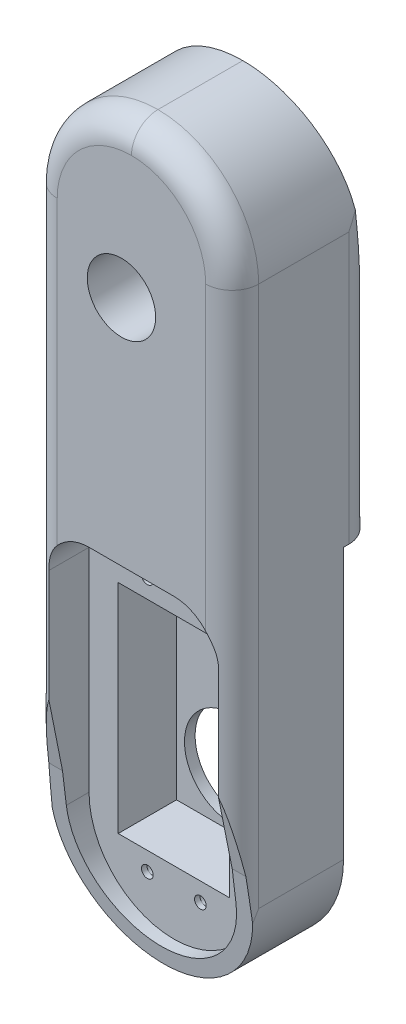
SolidWorks part; units mm, degrees
ref_plane "Front Plane" through (0, 0, 0) normal (0, 0, 1) x (1, 0, 0)
ref_plane "Top Plane" through (0, 0, 0) normal (0, 1, 0) x (1, 0, 0)
ref_plane "Right Plane" through (0, 0, 0) normal (1, 0, 0) x (0, 0, -1)
sketch "Sketch1" plane through (0, 0, 0) normal (0, 0, 1) x (1, 0, 0)
  line L5 (-19, -60) -> (19, -60)
  line L6 (-19, -60) -> (-19, 60)
  line L7 (-19, 60) -> (19, 60)
  line L8 (19, -60) -> (19, 60)
  line L9 (-19, -60) -> (19, 60) construction
  line L10 (-19, 60) -> (19, -60) construction
  line L11 (-10.5, -45) -> (10.5, -45)
  line L12 (-10.5, -45) -> (-10.5, -4)
  line L13 (-10.5, -4) -> (10.5, -4)
  line L14 (10.5, -45) -> (10.5, -4)
  line L15 (-10.5, -45) -> (10.5, -4) construction
  line L16 (-10.5, -4) -> (10.5, -45) construction
  point P0 (0, 0)
  point P6 (0, -24.5)
  dimension "D1" = 21
  dimension "D2" = 41
  dimension "D3" = 8.5
  dimension "D4" = 120
  dimension "D5" = 15
extrude "Boss-Extrude1" add sketch "Sketch1" along normal blind 11
ref_plane "Plane1" through (0, 0, 10) normal (0, 0, 1) x (1, 0, 0)
sketch "Sketch3" plane through (0, 0, 10) normal (0, 0, 1) x (1, 0, 0)
  line L0 (10.5, -4) -> (-10.5, -4) construction
  circle A0 centre (-5, -0.5) radius 1.3
  circle A1 centre (5, -0.5) radius 1.3
  circle A2 centre (5, -48.5) radius 1.3
  circle A3 centre (-5, -48.5) radius 1.3
  dimension "D1" = 2.6
  dimension "D2" = 5
  dimension "D3" = 3.5
  dimension "D4" = 2
  dimension "D5" = 2
extrude "Cut-Extrude1" cut sketch "Sketch3" against normal blind 8
fillet "Fillet3" radius 19 2 edges at (19, -60, 5.5) (-19, -60, 5.5)
sketch "Sketch4" plane through (0, 0, 11) normal (0, 0, 1) x (1, 0, 0)
  line L0 (16, -41) -> (16, 57)
  line L1 (16, 57) -> (-16, 57)
  line L2 (-16, 57) -> (-16, -41)
  line L3 (19, -41) -> (19, 60)
  line L4 (19, 60) -> (-19, 60)
  line L5 (-19, 60) -> (-19, -41)
  line L6 (19, -41) -> (19, 60)
  line L7 (19, 60) -> (-19, 60)
  line L8 (-19, 60) -> (-19, -41)
  arc A0 (-16, -41) -> (0, -57) centre (0, -41) ccw
  arc A1 (0, -57) -> (16, -41) centre (0, -41) ccw
  arc A2 (-19, -41) -> (0, -60) centre (0, -41) ccw
  arc A3 (0, -60) -> (19, -41) centre (0, -41) ccw
  arc A4 (-19, -41) -> (0, -60) centre (0, -41) ccw
  arc A5 (0, -60) -> (19, -41) centre (0, -41) ccw
  dimension "D1" = 0
  dimension "D2" = 3
extrude "Boss-Extrude2" add sketch "Sketch4" along normal blind 8
sketch "Sketch6" plane through (0, 0, 0) normal (1, 0, 0) x (0, 0, -1)
  line L7 (-13, -60) -> (-16, -35)
  line L8 (-16, -35) -> (-19, -20)
  line L9 (-19, -41) -> (-19, 60) construction
  line L10 (-19, -20) -> (-19, -60)
  line L11 (-19, -41) -> (-19, -60) construction
  line L12 (-19, -60) -> (-13, -60)
  line L13 (-11, -60) -> (0, -60) construction
  dimension "D1" = 6
  dimension "D2" = 25
  dimension "D3" = 15
  dimension "D4" = 3
extrude "Cut-Extrude2" cut sketch "Sketch6" against normal through all both and the other way through all
sketch "Sketch7" plane through (0, 0, 11) normal (0, 0, 1) x (1, 0, 0)
  line L0 (16, -20) -> (16, 57) construction
  line L1 (16, 7) -> (-16, 7)
  line L2 (16, 7) -> (16, 57)
  line L3 (16, 57) -> (-16, 57)
  line L4 (-16, 7) -> (-16, 57)
  dimension "D1" = 50
extrude "Boss-Extrude4" add sketch "Sketch7" along normal up to surface (8 mm away) up to face at (0, 19.25, 19)
sketch "Sketch8" plane through (0, 0, 0) normal (0, 0, -1) x (-1, 0, 0)
  line L0 (-19, 60) -> (19, 60)
  line L1 (19, 60) -> (19, -3.3108)
  line L2 (19, 60) -> (19, -41) construction
  line L3 (-19, 60) -> (-19, -4)
  line L4 (-19, -41) -> (-19, 60) construction
  line L7 (19, 10) -> (-19, 10)
  arc A0 (19, -3.3108) -> (-19, -4) centre (0.25, -17.4388) ccw
  line M2 (-19, 60) -> (-19, -41)
  line M6 (19, 60) -> (-19, 60)
  dimension "D1" = 23.4769
  dimension "D2" = 64
  dimension "D3" = 19.25
  dimension "D4" = 50
extrude "Boss-Extrude5" add sketch "Sketch8" along normal blind 8 contours L7 L1 M6 M2 region at (0, 35, 0)
sketch "Sketch27" plane through (0, 0, 0) normal (0, 0, -1) x (-1, 0, 0)
  line L0 (10.5, -45) -> (-10.5, -45) construction
  line L3 (19, -41) -> (19, 10)
  line L4 (19, 10) -> (-19, 10)
  line L5 (-19, 10) -> (-19, -41)
  line L6 (19, -41) -> (19, 10)
  line L7 (19, 10) -> (-19, 10)
  line L8 (-19, 10) -> (-19, -41)
  circle A0 centre (0, -34.75) radius 9
  arc A2 (-19, -41) -> (0, -60) centre (0, -41) ccw
  arc A3 (0, -60) -> (19, -41) centre (0, -41) ccw
  arc A4 (-19, -41) -> (0, -60) centre (0, -41) ccw
  arc A5 (0, -60) -> (19, -41) centre (0, -41) ccw
  dimension "D2" = 18
  dimension "D3" = 10.25
  dimension "D1" = 0
extrude "Boss-Extrude10" add sketch "Sketch27" along normal blind 2
sketch "Sketch28" plane through (0, 60, 0) normal (0, 1, 0) x (1, 0, 0)
  line L4 (19, -19) -> (19, 8)
  line L5 (19, 8) -> (-19, 8)
  line L6 (-19, 8) -> (-19, -19)
  line L7 (-19, -19) -> (19, -19)
  line L8 (19, -19) -> (19, 8)
  line L9 (19, 8) -> (-19, 8)
  line L10 (-19, 8) -> (-19, -19)
  line L11 (-19, -19) -> (19, -19)
  dimension "D1" = 0
extrude "Boss-Extrude11" add sketch "Sketch28" along normal blind 20
fillet "Fillet4" radius 19 2 edges at (-19, 80, 5.5) (19, 80, 5.5)
sketch "Sketch29" plane through (0, 0, -8) normal (0, 0, -1) x (-1, 0, 0)
  line L6 (16, 13) -> (16, 61)
  line L7 (-16, 61) -> (-16, 13)
  line L8 (-16, 13) -> (16, 13)
  line L9 (16, 13) -> (16, 61)
  line L10 (-16, 61) -> (-16, 13)
  line L11 (-16, 13) -> (16, 13)
  arc A4 (16, 61) -> (0, 77) centre (0, 61) ccw
  arc A5 (0, 77) -> (-16, 61) centre (0, 61) ccw
  arc A6 (16, 61) -> (0, 77) centre (0, 61) ccw
  arc A7 (0, 77) -> (-16, 61) centre (0, 61) ccw
  dimension "D1" = 3
extrude "Cut-Extrude14" cut sketch "Sketch29" against normal blind 8
sketch "Sketch30" plane through (0, 0, 0) normal (0, 0, -1) x (-1, 0, 0)
  line L0 (-16, 13) -> (16, 13) construction
  line L1 (-4.6176, 34.5) -> (8.3824, 34.5)
  line L2 (-4.6176, 34.5) -> (-4.6176, 57.5)
  line L3 (-4.6176, 57.5) -> (8.3824, 57.5)
  line L4 (8.3824, 34.5) -> (8.3824, 57.5)
  line L5 (-4.6176, 34.5) -> (8.3824, 57.5) construction
  line L6 (-4.6176, 57.5) -> (8.3824, 34.5) construction
  point P0 (1.8824, 46)
  point P11 (1.7246, 48.9756)
  point P12 (-4.6176, 38.4784)
  dimension "D3" = 11.5
  dimension "D1" = 13
  dimension "D2" = 21.5
  dimension "D4" = 23
sketch "Sketch32" plane through (0, 0, 19) normal (0, 0, 1) x (1, 0, 0)
  line L0 (-19, 12) -> (19, 12)
  line L7 (-19, 61) -> (-19, -20)
  line L8 (-19, -20) -> (-16, -20)
  line L9 (-16, -20) -> (-16, 7)
  line L10 (-16, 7) -> (16, 7)
  line L11 (16, 7) -> (16, -20)
  line L12 (16, -20) -> (19, -20)
  line L13 (19, -20) -> (19, 61)
  line L14 (-19, 61) -> (-19, -20)
  line L15 (-19, -20) -> (-16, -20)
  line L16 (-16, -20) -> (-16, 7)
  line L17 (-16, 7) -> (16, 7)
  line L18 (16, 7) -> (16, -20)
  line L19 (16, -20) -> (19, -20)
  line L20 (19, -20) -> (19, 61)
  arc A2 (19, 61) -> (0, 80) centre (0, 61) ccw
  arc A3 (0, 80) -> (-19, 61) centre (0, 61) ccw
  arc A4 (19, 61) -> (0, 80) centre (0, 61) ccw
  arc A5 (0, 80) -> (-19, 61) centre (0, 61) ccw
  dimension "D2" = 5
  dimension "D1" = 0
sketch "Sketch33" plane through (19, 0, 0) normal (1, 0, 0) x (0, 0, -1)
  line L0 (2, 80) -> (8, 40)
  line L1 (-13, 80) -> (8, 80) construction
  line L2 (8, 61) -> (8, 10) construction
  line L3 (2, 80) -> (8, 80)
  line L4 (8, 80) -> (8, 40)
  dimension "D1" = 6
  dimension "D2" = 40
extrude "Cut-Extrude18" cut sketch "Sketch33" against normal through all
fillet "Fillet7" radius 5 6 edges at (-19, 25, -8) (19, 25, -8) (-19, 20.5, 19) (19, 20.5, 19) (-13.435, 74.435, 19) (13.435, 74.435, 19)
sketch "Sketch35" plane through (0, 0, 11) normal (0, 0, 1) x (1, 0, 0)
  line L0 (10.5, -4) -> (-10.5, -4) construction
  line L1 (0, 0) -> (0, -6.946) construction
  circle A0 centre (-5, -0.5) radius 1.1
  circle A1 centre (5, -0.5) radius 1.1
  circle A2 centre (5, -48.5) radius 1.1
  circle A3 centre (-5, -48.5) radius 1.1
  dimension "D1" = 2.2
  dimension "D2" = 5
  dimension "D3" = 3.5
  dimension "D4" = 2
  dimension "D5" = 2
extrude "Cut-Extrude20" cut sketch "Sketch35" against normal blind 8
fillet "Fillet8" radius 8 4 edges at (-16, 7, 14.7913) (16, 7, 14.7913) (16, 13, -3.7913) (-16, 13, -3.7913)
sketch "Sketch36" plane through (0, 0, 0) normal (0, 0, -1) x (-1, 0, 0)
  circle A0 centre (1.8824, 50.8321) radius 6.45
  point P4 (1.8824, 57.5)
  point P5 (0, 0)
  dimension "D1" = 12.9
extrude "Cut-Extrude21" cut sketch "Sketch36" against normal through all
extrude "Cut-Extrude22" cut sketch "Sketch30" against normal blind 8.5
